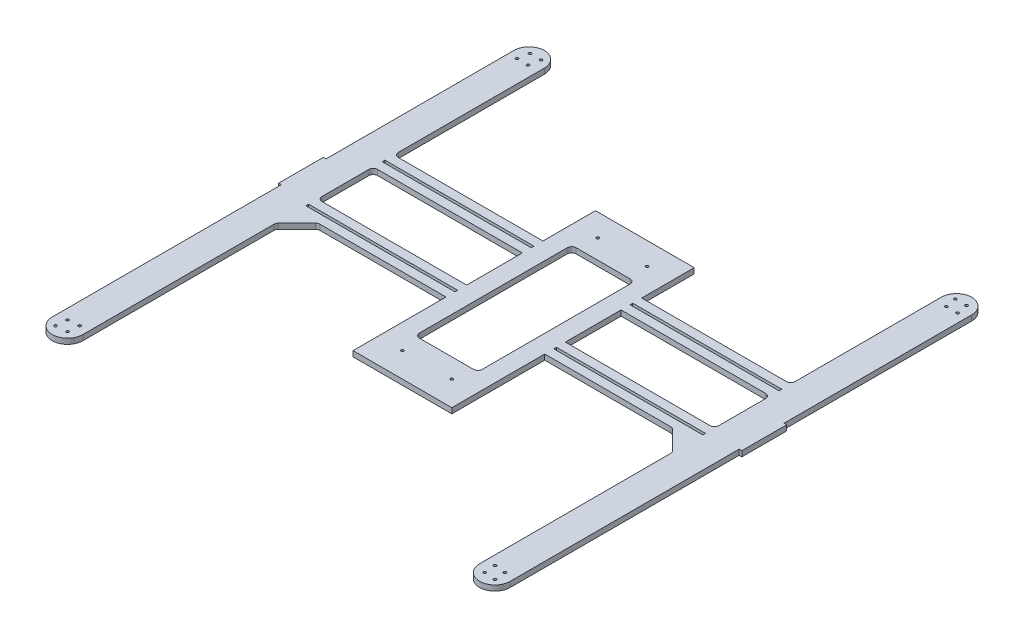
SolidWorks part; units mm, degrees
ref_plane "Front Plane" through (0, 0, 0) normal (0, 0, 1) x (1, 0, 0)
ref_plane "Top Plane" through (0, 0, 0) normal (0, 1, 0) x (1, 0, 0)
ref_plane "Right Plane" through (0, 0, 0) normal (1, 0, 0) x (0, 0, -1)
sketch "Sketch1" plane through (0, 0, 0) normal (0, 1, 0) x (1, 0, 0)
  line L1 (216, -40) -> (216, -255)
  line L4 (216, 78.5) -> (216, 81.5)
  line L5 (250, -255) -> (250, 0)
  line L6 (50, -120) -> (250, -120) construction
  line L7 (50, 150) -> (50, 91.5) construction
  line L8 (50, 150) -> (250, 120) construction
  line L10 (227.9078, 252.8902) -> (238.0922, 265.2304) construction
  line L11 (240.327, 253.0134) -> (225.673, 265.1073) construction
  line L12 (227.3431, -260.6569) -> (238.6569, -249.3431) construction
  line L13 (0, 25) -> (250, 25) construction
  line L14 (226.2825, -248.2825) -> (239.7175, -261.7175) construction
  line L18 (250, 0) -> (253, 0)
  line L19 (253, 0) -> (253, 50)
  line L20 (253, 50) -> (250, 50)
  line L21 (250, 50) -> (250, 259.0603)
  line L22 (50, 81.5) -> (50, 78.5) construction
  line L23 (50, 81.5) -> (50, 78.5)
  line L24 (50, -3.5) -> (50, -6.5) construction
  line L25 (50, -16.5) -> (50, -120) construction
  line L26 (50, 68.5) -> (50, 6.5)
  line L27 (-60, -5) -> (-226, -5) construction
  line L28 (216, 68.5) -> (216, 6.5)
  line L29 (-226, 68.5) -> (-226, 6.5)
  line L47 (-5, 150) -> (-5, -120) construction
  line L48 (-60, -120) -> (50, -120)
  line L53 (-60, 150) -> (50, 150)
  line L54 (50, 150) -> (50, 91.5)
  line L57 (250, -120) -> (250, -5) construction
  line L58 (50, -3.5) -> (50, -6.5)
  line L59 (216, -6.5) -> (50, -6.5)
  line L60 (50, 80) -> (216, 80) construction
  line L61 (250, 80) -> (250, 81.5) construction
  line L62 (216, 81.5) -> (50, 81.5)
  line L63 (216, -3.5) -> (50, -3.5)
  line L64 (250, 80) -> (250, 78.5) construction
  line L65 (216, 78.5) -> (50, 78.5)
  line L66 (-60, 80) -> (-226, 80) construction
  line L67 (50, 91.5) -> (216, 91.5)
  line L68 (-260, -120) -> (-260, -5) construction
  line L69 (50, 68.5) -> (216, 68.5)
  line L70 (50, -120) -> (50, -16.5)
  line L71 (-60, -16.5) -> (-60, -120) construction
  line L72 (50, -16.5) -> (192.5, -16.5)
  line L73 (-60, -3.5) -> (-60, -6.5) construction
  line L74 (50, 6.5) -> (216, 6.5)
  line L75 (192.5, -16.5) -> (216, -40)
  line L76 (50, -5) -> (216, -5) construction
  line L79 (216, -6.5) -> (216, -3.5)
  line L80 (216, 91.5) -> (216, 259.0603)
  line L81 (-60, 81.5) -> (-60, 78.5) construction
  line L82 (-236.2825, -248.2825) -> (-249.7175, -261.7175) construction
  line L83 (-10, 25) -> (-260, 25) construction
  line L84 (-237.3431, -260.6569) -> (-248.6569, -249.3431) construction
  line L85 (-250.327, 253.0134) -> (-235.673, 265.1073) construction
  line L86 (-237.9078, 252.8902) -> (-248.0922, 265.2304) construction
  line L87 (-60, 150) -> (-260, 120) construction
  line L88 (-60, 150) -> (-60, 91.5) construction
  line L89 (-60, -120) -> (-260, -120) construction
  line L90 (-226, 91.5) -> (-226, 259.0603)
  line L91 (-226, -6.5) -> (-226, -3.5)
  line L93 (-202.5, -16.5) -> (-226, -40)
  line L94 (-60, 6.5) -> (-226, 6.5)
  line L95 (-60, -16.5) -> (-202.5, -16.5)
  line L96 (-60, -120) -> (-60, -16.5)
  line L97 (-60, 68.5) -> (-226, 68.5)
  line L98 (-60, 91.5) -> (-226, 91.5)
  line L99 (-226, 78.5) -> (-60, 78.5)
  line L100 (-226, -3.5) -> (-60, -3.5)
  line L101 (-226, 81.5) -> (-60, 81.5)
  line L102 (-226, -6.5) -> (-60, -6.5)
  line L103 (-60, -3.5) -> (-60, -6.5)
  line L104 (-60, 150) -> (-60, 91.5)
  line L105 (-60, 68.5) -> (-60, 6.5)
  line L106 (-60, 81.5) -> (-60, 78.5)
  line L107 (-260, 50) -> (-260, 259.0603)
  line L108 (-263, 50) -> (-260, 50)
  line L109 (-263, 0) -> (-263, 50)
  line L110 (-260, 0) -> (-263, 0)
  line L111 (-260, -255) -> (-260, 0)
  line L112 (-226, 78.5) -> (-226, 81.5)
  line L113 (-226, -40) -> (-226, -255)
  line L121 (30, 103.5) -> (30, -71)
  line L122 (30, 103.5) -> (-40, 103.5)
  line L123 (-40, 103.5) -> (-40, -71)
  line L124 (-40, -71) -> (30, -71)
  arc A0 (216, -255) -> (250, -255) centre (233, -255) ccw
  arc A1 (216, 259.0603) -> (250, 259.0603) centre (233, 259.0603) cw
  circle A2 centre (233, -255) radius 135 construction
  circle A3 centre (233, 259.0603) radius 135 construction
  circle A4 centre (238.0922, 265.2304) radius 1.5
  circle A5 centre (225.673, 265.1073) radius 1.5
  circle A6 centre (227.9078, 252.8902) radius 1.5
  circle A7 centre (240.327, 253.0134) radius 1.5
  circle A8 centre (226.2825, -248.2825) radius 1.5
  circle A9 centre (238.6569, -249.3431) radius 1.5
  circle A10 centre (239.7175, -261.7175) radius 1.5
  circle A11 centre (227.3431, -260.6569) radius 1.5
  circle A33 centre (22.5, 125) radius 1.5
  circle A36 centre (-243, 259.0603) radius 135 construction
  circle A37 centre (-243, -255) radius 135 construction
  circle A39 centre (-32.5, 125) radius 1.5
  circle A40 centre (-237.3431, -260.6569) radius 1.5
  circle A41 centre (-249.7175, -261.7175) radius 1.5
  circle A42 centre (-248.6569, -249.3431) radius 1.5
  circle A43 centre (-236.2825, -248.2825) radius 1.5
  circle A44 centre (-250.327, 253.0134) radius 1.5
  circle A45 centre (-237.9078, 252.8902) radius 1.5
  circle A46 centre (-235.673, 265.1073) radius 1.5
  circle A47 centre (-248.0922, 265.2304) radius 1.5
  arc A48 (-226, 259.0603) -> (-260, 259.0603) centre (-243, 259.0603) ccw
  arc A49 (-226, -255) -> (-260, -255) centre (-243, -255) cw
  circle A50 centre (22.5, -92.5) radius 1.5
  circle A51 centre (-32.5, -92.5) radius 1.5
  point P12 (250, 120)
  point P13 (250, -120)
  point P15 (50, -120)
  point P134 (-60, -120)
  point P135 (-260, -120)
  point P136 (-260, 120)
  dimension "D1" = 17
  dimension "D3" = 270
  dimension "D4" = 270
  dimension "D12" = 3
  dimension "D13" = 3
  dimension "D14" = 3
  dimension "D15" = 3
  dimension "D20" = 3
  dimension "D21" = 3
  dimension "D22" = 3
  dimension "D23" = 3
  dimension "D5" = 240
  dimension "D6" = 200
  dimension "D9" = 16
  dimension "D10" = 19
  dimension "D16" = 270
  dimension "D17" = 45
  dimension "D18" = 16
  dimension "D19" = 19
extrude "Boss-Extrude1" add sketch "Sketch1" along normal blind 6 contours L1 A0 L5 L8 L4 L7 A11 A10 A9 A8 | L7 | A1 L4 L8 L5 A7 A6 A5 A4 region at (209.5727, 0, 22.9273)
fillet "Скругление1" radius 5 14 edges at (216, 3, -6.5) (216, 3, -68.5) (216, 3, -91.5) (-226, 3, -6.5) (-226, 3, -68.5) (-226, 3, -91.5) (-226, 3, 40) (-202.5, 3, 16.5) (216, 3, 40) (192.5, 3, 16.5) (-40, 3, 71) (30, 3, 71) (30, 3, -103.5) (-40, 3, -103.5)
